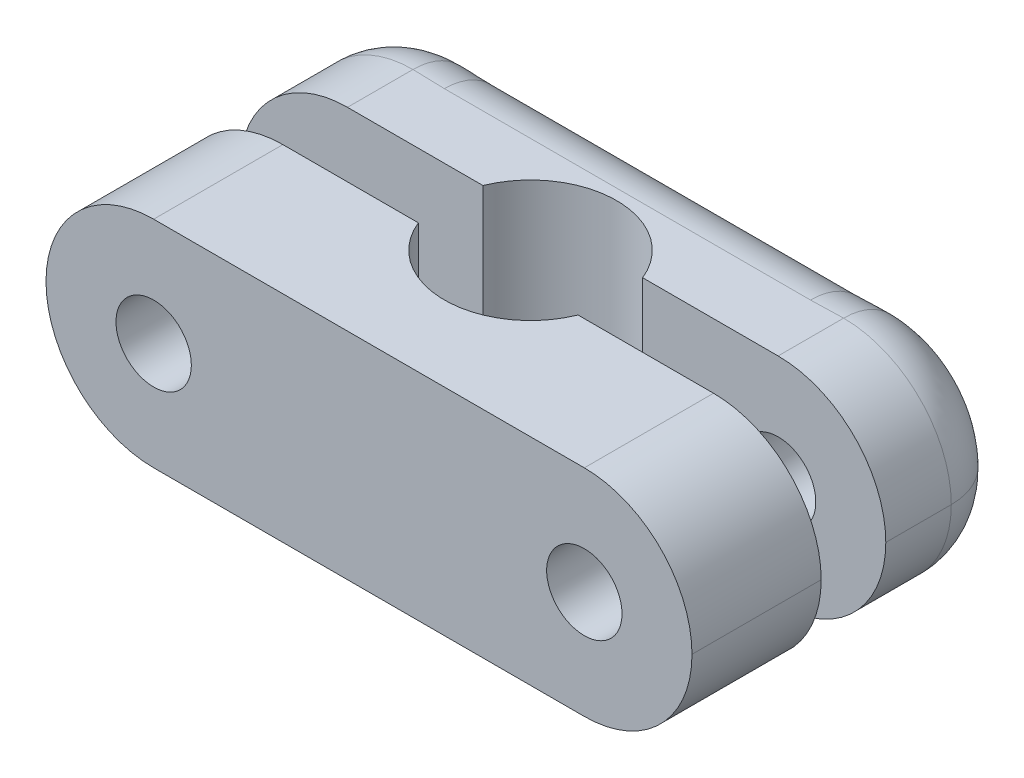
SolidWorks part; units mm, degrees
material "ABS"
ref_plane "Front Plane" through (0, 0, 0) normal (0, 0, 1) x (1, 0, 0)
ref_plane "Top Plane" through (0, 0, 0) normal (0, 1, 0) x (1, 0, 0)
ref_plane "Right Plane" through (0, 0, 0) normal (1, 0, 0) x (0, 0, -1)
sketch "Sketch1" plane through (0, 0, 0) normal (0, 1, 0) x (1, 0, 0)
  line L1 (-15, -7.5) -> (15, -7.5)
  line L2 (-15, -7.5) -> (-15, 7.5)
  line L3 (-15, 7.5) -> (15, 7.5)
  line L4 (15, -7.5) -> (15, 7.5)
  line L5 (-15, -7.5) -> (15, 7.5) construction
  line L6 (-15, 7.5) -> (15, -7.5) construction
  point P0 (0, 0)
  dimension "D1" = 30
  dimension "D2" = 15
extrude "Boss-Extrude1" add sketch "Sketch1" along normal blind 10
sketch "Sketch2" plane through (0, 10, 0) normal (0, 1, 0) x (1, 0, 0)
  circle A0 centre (0, 0) radius 4
  dimension "D1" = 8
extrude "Cut-Extrude1" cut sketch "Sketch2" against normal blind 10
sketch "Sketch3" plane through (0, 0, 7.5) normal (0, 0, 1) x (1, 0, 0)
  line L0 (-15, 0) -> (15, 0) construction
  line L1 (-15, 10) -> (-15, 0) construction
  circle A0 centre (-10, 5) radius 1.75
  circle A1 centre (10, 5) radius 1.75
  dimension "D1" = 3.5
  dimension "D5" = 3.5
  dimension "D2" = 5
  dimension "D3" = 5
  dimension "D4" = 20
extrude "Cut-Extrude2" cut sketch "Sketch3" against normal through all
sketch "Sketch4" plane through (0, 0, -7.5) normal (0, 0, -1) x (-1, 0, 0)
  circle A0 centre (-10, 5) radius 2.5
  circle A1 centre (10, 5) radius 2.5
  dimension "D1" = 5
  dimension "D2" = 5
extrude "Cut-Extrude3" cut sketch "Sketch4" against normal blind 3.5
sketch "Sketch5" plane through (0, 10, 0) normal (0, 1, 0) x (1, 0, 0)
  line L0 (-15, 7.5) -> (-15, -7.5) construction
  line L1 (15, 1.5) -> (-15, 1.5)
  line L2 (15, 1.5) -> (15, -1.5)
  line L3 (15, -1.5) -> (-15, -1.5)
  line L4 (-15, 1.5) -> (-15, -1.5)
  line L5 (15, 1.5) -> (-15, -1.5) construction
  line L6 (15, -1.5) -> (-15, 1.5) construction
  point P0 (0, 0)
  dimension "D1" = 3
extrude "Cut-Extrude4" cut sketch "Sketch5" against normal through all
fillet "Fillet3" radius 5 4 edges at (15, 10, 4.5) (15, 0, 4.5) (-15, 0, 4.5) (-15, 10, 4.5)
fillet "Fillet4" radius 5 4 edges at (15, 0, -4.5) (15, 10, -4.5) (-15, 0, -4.5) (-15, 10, -4.5)
fillet "Fillet2" radius 3 2 edges at (0, 10, -7.5) (0, 0, -7.5)
